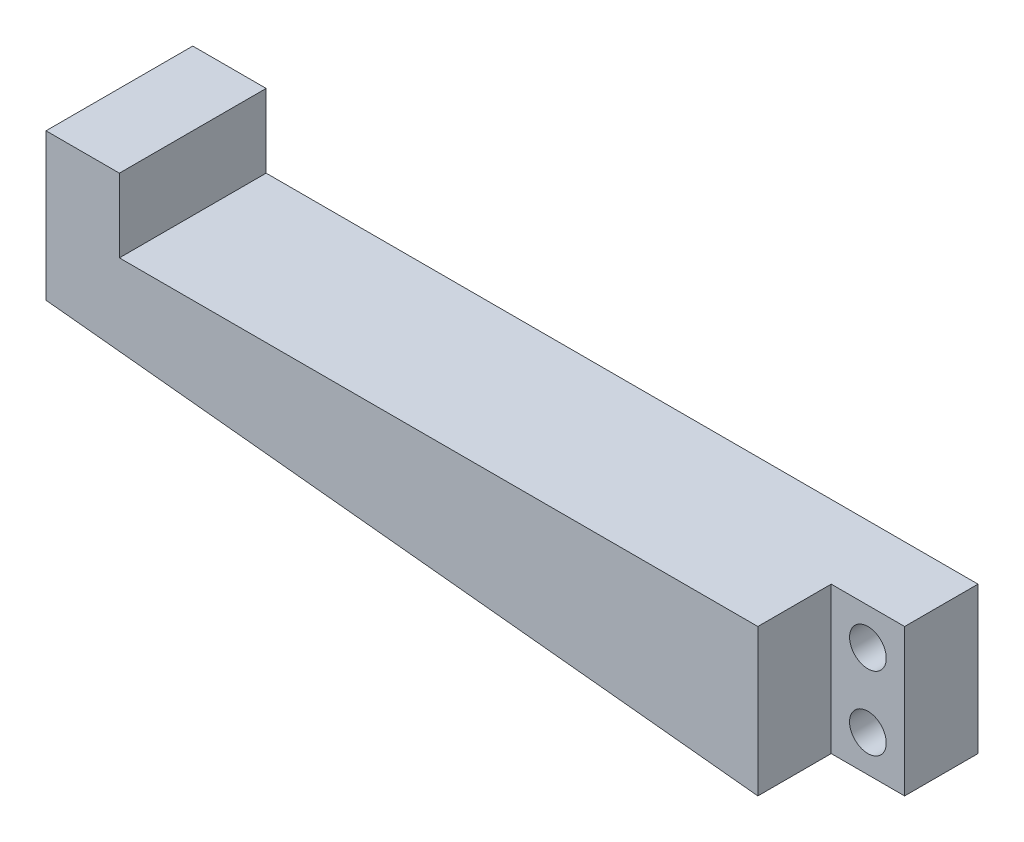
SolidWorks part; units mm, degrees
ref_plane "Plan de face" through (0, 0, 0) normal (0, 0, 1) x (1, 0, 0)
ref_plane "Plan de dessus" through (0, 0, 0) normal (0, 1, 0) x (1, 0, 0)
ref_plane "Plan de droite" through (0, 0, 0) normal (1, 0, 0) x (0, 0, -1)
sketch "Esquisse1" plane through (0, 0, 0) normal (0, 0, 1) x (1, 0, 0)
  line L0 (-102, 0) -> (-5, -10)
  line L1 (-5, -10) -> (5, -10)
  line L3 (-5, 10) -> (5, 10)
  line L4 (5, -10) -> (5, 10)
  line L5 (-5, -10) -> (5, 10) construction
  line L6 (-5, 10) -> (5, -10) construction
  line L7 (-5, 10) -> (-92, 10)
  line L10 (-102, 10) -> (-102, 0)
  line L12 (-102, 10) -> (-102, 20)
  line L13 (-102, 20) -> (-92, 20)
  line L14 (-92, 10) -> (-92, 20)
  circle A0 centre (0, 5) radius 2.5
  circle A1 centre (0, -5) radius 2.5
  point P0 (0, 0)
  dimension "D2" = 5
  dimension "D6" = 5
  dimension "D1" = 20
  dimension "D3" = 10
  dimension "D4" = 5
  dimension "D5" = 5
  dimension "D7" = 97
  dimension "D8" = 10
  dimension "D9" = 10
  dimension "D10" = 10
extrude "Boss.-Extru.1" add sketch "Esquisse1" along normal blind 20
sketch "Esquisse2" plane through (0, 0, 20) normal (0, 0, 1) x (1, 0, 0)
  line L1 (-5, -10) -> (5, -10)
  line L2 (-5, -10) -> (-5, 10)
  line L3 (-5, 10) -> (5, 10)
  line L4 (5, -10) -> (5, 10)
extrude "Enlèv. mat.-Extru.1" cut sketch "Esquisse2" against normal blind 10
